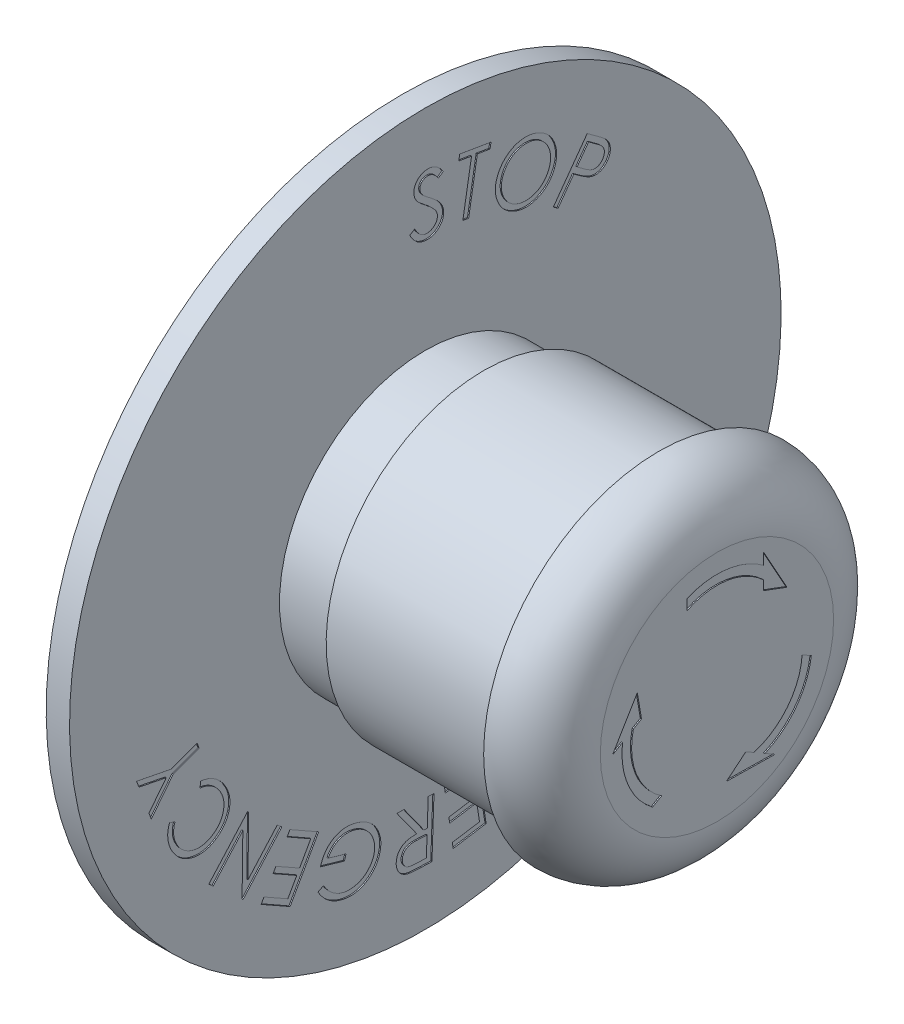
SolidWorks part; units mm, degrees
ref_plane "Ön Düzlem" through (0, 0, 0) normal (0, 0, 1) x (1, 0, 0)
ref_plane "Üst Düzlem" through (0, 0, 0) normal (0, 1, 0) x (1, 0, 0)
ref_plane "Sağ Düzlem" through (0, 0, 0) normal (1, 0, 0) x (0, 0, -1)
sketch "Çizim1" plane through (0, 0, 0) normal (0, 0, 1) x (1, 0, 0)
  line L0 (0, 0) -> (0, 11)
  line L1 (0, 11) -> (5, 11)
  line L2 (5, 11) -> (5, 30.5)
  line L3 (5, 30.5) -> (7, 30.5)
  line L4 (7, 30.5) -> (7, 12.5)
  line L5 (7, 12.5) -> (12, 12.5)
  line L6 (12, 12.5) -> (12, 13.5)
  line L7 (12, 13.5) -> (27, 13.5)
  line L8 (27, 13.5) -> (27, 15)
  line L9 (27, 15) -> (32, 15)
  line L10 (32, 15) -> (32, 0)
  line L11 (32, 0) -> (0, 0) construction
  line L12 (0, 0) -> (32, 0)
  dimension "D1" = 22
  dimension "D2" = 61
  dimension "D3" = 2
  dimension "D4" = 25
  dimension "D5" = 25
  dimension "D6" = 27
  dimension "D7" = 30
  dimension "D8" = 5
  dimension "D9" = 15
  dimension "D10" = 5
revolve "Döndür1" add sketch "Çizim1" angle 360 about L11
fillet "Radyus1" radius 5 1 edges at (32, 15, 0)
sketch "Çizim2" plane through (7, 0, 0) normal (1, 0, 0) x (0, 0, -1)
  circle A0 centre (0, 0) radius 20.8333 construction
  text T0 "EMERGENCY                   STOP" font "Century Gothic" height 5
extrude "Kes-Ekstrüzyon1" cut sketch "Çizim2" against normal blind 0.1
sketch "Çizim3" plane through (32, 0, 0) normal (1, 0, 0) x (0, 0, -1)
  line L0 (-2.5631, 7.8611) -> (-2.5631, 6.9546)
  line L1 (8.0895, -1.7109) -> (7.3044, -1.2576)
  line L2 (3.9907, 7.0451) -> (3.9907, 8.0399)
  line L3 (3.9907, 8.0399) -> (6.0062, 4.4121)
  line L4 (6.0062, 4.4121) -> (3.9907, 5.164)
  line L5 (3.9907, 5.164) -> (3.9907, 5.9678)
  line L6 (4.1058, -6.9786) -> (4.9674, -7.476)
  line L7 (4.9674, -7.476) -> (0.8179, -7.4076)
  line L8 (0.8179, -7.4076) -> (2.4768, -6.0381)
  line L9 (2.4768, -6.0381) -> (3.1729, -6.44)
  line L10 (-5.5264, -6.1502) -> (-4.7414, -5.697)
  line L11 (-8.0966, -0.0665) -> (-8.9581, -0.5639)
  line L12 (-8.9581, -0.5639) -> (-6.8241, 2.9954)
  line L13 (-6.8241, 2.9954) -> (-6.4675, 0.8741)
  line L14 (-6.4675, 0.8741) -> (-7.1637, 0.4722)
  arc A0 (3.9907, 5.9678) -> (-2.5631, 6.9546) centre (0, 1.7203) ccw
  arc A1 (3.9907, 7.0451) -> (-2.5631, 7.8611) centre (0, 1.7203) ccw
  arc A2 (3.1729, -6.44) -> (7.3044, -1.2576) centre (1.4898, -0.8601) ccw
  arc A3 (4.1058, -6.9786) -> (8.0895, -1.7109) centre (1.4898, -0.8601) ccw
  arc A4 (-7.1637, 0.4722) -> (-4.7414, -5.697) centre (-1.4898, -0.8601) ccw
  arc A5 (-8.0966, -0.0665) -> (-5.5264, -6.1502) centre (-1.4898, -0.8601) ccw
  point P26 (0, 0)
  dimension "D1" = 3
extrude "Kes-Ekstrüzyon2" cut sketch "Çizim3" against normal blind 0.1
